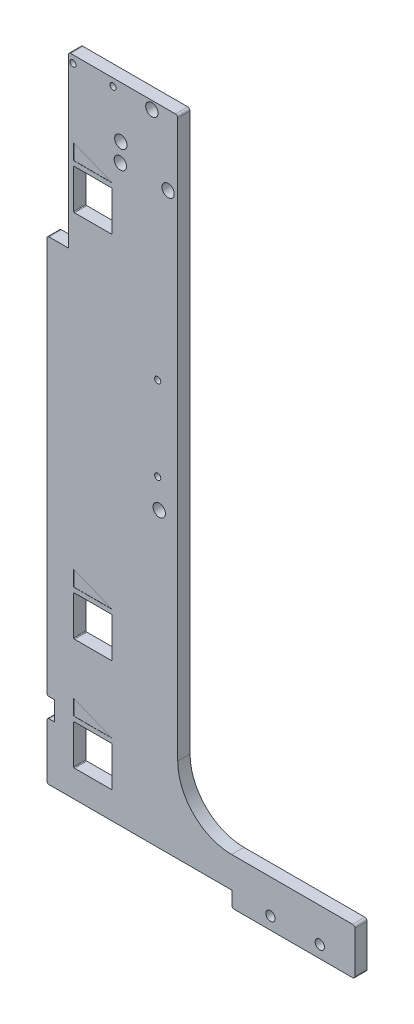
SolidWorks part; units mm, degrees
material "metacrilato"
ref_plane "Alzado" through (0, 0, 0) normal (0, 0, 1) x (1, 0, 0)
ref_plane "Planta" through (0, 0, 0) normal (0, 1, 0) x (1, 0, 0)
ref_plane "Vista lateral" through (0, 0, 0) normal (1, 0, 0) x (0, 0, -1)
sketch "Croquis1" plane through (0, 0, 0) normal (0, 0, 1) x (1, 0, 0)
  line L0 (0, 0) -> (-200, 0)
  line L1 (-200, 0) -> (-200, 428)
  line L2 (-200, 428) -> (-115, 428)
  line L3 (-115, 428) -> (-115, 30)
  line L4 (-115, 30) -> (0, 30)
  line L5 (0, 30) -> (0, 0)
  dimension "D1" = 200
  dimension "D2" = 428
  dimension "D3" = 30
  dimension "D4" = 85
extrude "Base" add sketch "Croquis1" along normal mid plane 8
fillet "Redondeo1" radius 35 1 edges at (-115, 30, 0)
sketch "Croquis2" plane through (0, 0, 4) normal (0, 0, 1) x (1, 0, 0)
  line L0 (-115, 428) -> (-200, 428) construction
  line L1 (-200, 428) -> (-200, 0) construction
  line L3 (0, 0) -> (0, 30) construction
  line L4 (-200, 0) -> (0, 0) construction
  circle A0 centre (-183, 423.2) radius 2
  circle A1 centre (-157, 423.2) radius 2
  circle A2 centre (-128, 272.65) radius 2
  circle A3 centre (-128, 218.35) radius 2
  circle A4 centre (-54.8, 8) radius 3
  circle A5 centre (-22.8, 8) radius 3
  dimension "D1" = 4
  dimension "D2" = 4.8
  dimension "D3" = 17
  dimension "D4" = 26
  dimension "D5" = 54.3
  dimension "D6" = 72
  dimension "D7" = 155.35
  dimension "D9" = 6
  dimension "D10" = 22.8
  dimension "D8" = 32
  dimension "D11" = 8
extrude "Forats guia Left" cut sketch "Croquis2" against normal up to next
sketch "Croquis3" plane through (0, 0, 4) normal (0, 0, 1) x (1, 0, 0)
  circle A0 centre (-127, 176.5) radius 4
  circle A1 centre (-128, 218.35) radius 2 construction
  circle A2 centre (-91.3, 19) radius 4
  circle A3 centre (-127.3, 19) radius 4
  circle A7 centre (-54.8, 8) radius 3 construction
  dimension "D1" = 8
  dimension "D2" = 41.85
  dimension "D3" = 1
  dimension "D4" = 11
  dimension "D5" = 36.5
  dimension "D6" = 36
extrude "Forats Left" [suppressed] cut sketch "Croquis3" against normal through all
sketch "Croquis4" plane through (0, 0, -4) normal (0, 0, -1) x (-1, 0, 0)
  line L0 (115, 65) -> (115, 428) construction
  line L1 (115, 428) -> (200, 428) construction
  circle A0 centre (131.8, 422.75) radius 4
  circle A1 centre (151.95, 394.65) radius 4
  circle A2 centre (152.25, 382.59) radius 4
  circle A3 centre (121.25, 382.59) radius 4
  circle A4 centre (127, 200) radius 4
  point P12 (127, 176.5)
  dimension "D1" = 8
  dimension "D2" = 16.8
  dimension "D3" = 5.25
  dimension "D5" = 33.35
  dimension "D6" = 45.41
  dimension "D8" = 31
  dimension "D10" = 12
  dimension "D9" = 228
  dimension "D4" = 36.95
  dimension "D7" = 6.25
extrude "Forats Right" cut sketch "Croquis4" against normal up to next
sketch "Croquis5" plane through (0, 0, 4) normal (0, 0, 1) x (1, 0, 0)
  line L0 (-200, 428) -> (-200, 0) construction
  line L1 (-182.5, 53.5) -> (-157.5, 53.5)
  line L2 (-182.5, 53.5) -> (-182.5, 27.5)
  line L3 (-182.5, 27.5) -> (-157.5, 27.5)
  line L4 (-157.5, 53.5) -> (-157.5, 27.5)
  line L5 (-182.5, 126) -> (-157.5, 126)
  line L6 (-182.5, 126) -> (-182.5, 100)
  line L7 (-182.5, 100) -> (-157.5, 100)
  line L8 (-157.5, 126) -> (-157.5, 100)
  line L9 (-182.5, 365.7) -> (-157.5, 365.7)
  line L10 (-182.5, 365.7) -> (-182.5, 339.7)
  line L11 (-182.5, 339.7) -> (-157.5, 339.7)
  line L12 (-157.5, 365.7) -> (-157.5, 339.7)
  line L13 (-200, 0) -> (0, 0) construction
  dimension "D1" = 25
  dimension "D2" = 26
  dimension "D3" = 17.5
  dimension "D4" = 27.5
  dimension "D5" = 100
  dimension "D6" = 339.7
extrude "Tatxueles" cut sketch "Croquis5" against normal up to next
fillet "Redondeo3" radius 0.5 12 edges at (-182.5, 53.5, 0) (-157.5, 53.5, 0) (-182.5, 27.5, 0) (-182.5, 126, 0) (-157.5, 126, 0) (-157.5, 100, 0) (-182.5, 100, 0) (-182.5, 365.7, 0) (-157.5, 365.7, 0) (-157.5, 339.7, 0) (-182.5, 339.7, 0) (-157.5, 27.5, 0)
sketch "Croquis7" plane through (0, 0, 4) normal (0, 0, 1) x (1, 0, 0)
  line L0 (-200, 0) -> (0, 0) construction
  line L1 (-79.8, 0) -> (-200, 0)
  line L2 (-79.8, 0) -> (-79.8, 10)
  line L3 (-79.8, 10) -> (-200, 10)
  line L4 (-200, 0) -> (-200, 10)
  line L5 (-200, 428) -> (-200, 0) construction
  line L6 (-115, 428) -> (-200, 428) construction
  line L7 (-200, 336.7) -> (-186, 336.7)
  line L8 (-200, 336.7) -> (-200, 428)
  line L9 (-200, 428) -> (-186, 428)
  line L10 (-186, 336.7) -> (-186, 428)
  line L11 (-182.5, 365.2) -> (-182.5, 340.2) construction
  line L14 (-200, 59.5) -> (-195, 59.5)
  line L15 (-200, 59.5) -> (-200, 47)
  line L16 (-200, 47) -> (-195, 47)
  line L17 (-195, 59.5) -> (-195, 47)
  line L18 (-200, 336.7) -> (-187.5, 336.7)
  line L19 (-200, 336.7) -> (-200, 319.2)
  line L20 (-200, 319.2) -> (-187.5, 319.2)
  line L21 (-187.5, 336.7) -> (-187.5, 319.2)
  line L22 (-115, 428) -> (-200, 428) construction
  circle A0 centre (-54.8, 8) radius 3 construction
  line M43 (-115, 428) -> (-200, 428)
  line M44 (-200, 428) -> (-200, 0)
  dimension "D1" = 10
  dimension "D2" = 25
  dimension "D3" = 3.5
  dimension "D4" = 91.3
  dimension "D5" = 12.5
  dimension "D6" = 17.5
  dimension "D7" = 12.5
  dimension "D8" = 5
  dimension "D9" = 47
extrude "Geometria exterior" cut sketch "Croquis7" against normal up to next contours L17 L14 L16 M44 | L7 L10 M43 M44 | L21 L18 L7 L20 M44 | L3 L4 L1 L2 region at (-193.75, 327.95, 4) region at (-197.5, 53.25, 4) region at (-193, 382.35, 4)
sketch "Croquis8" plane through (0, 0, 4) normal (0, 0, 1) x (1, 0, 0)
  line L0 (-182.5, 66.5) -> (-182.5, 56.5)
  line L1 (-182.5, 56.5) -> (-157.5, 56.5)
  line L2 (-157.5, 56.5) -> (-182.5, 66.5)
  line L3 (-182.5, 129) -> (-182.5, 139)
  line L4 (-182.5, 139) -> (-157.5, 129)
  line L5 (-157.5, 129) -> (-182.5, 129)
  line L6 (-182.5, 368.7) -> (-182.5, 378.7)
  line L7 (-182.5, 378.7) -> (-157.5, 368.7)
  line L8 (-157.5, 368.7) -> (-182.5, 368.7)
  line L9 (-170, 56.5) -> (-170, 53.5) construction
  line L10 (-157.5, 340.2) -> (-157.5, 365.2) construction
  line L11 (-158, 53.5) -> (-182, 53.5) construction
  line L12 (-170, 129) -> (-170, 126) construction
  line L13 (-158, 126) -> (-182, 126) construction
  line L14 (-170, 368.7) -> (-170, 365.7) construction
  line L15 (-158, 365.7) -> (-182, 365.7) construction
  dimension "D1" = 10
  dimension "D2" = 3
extrude "Triangles" cut sketch "Croquis8" against normal blind 0.1
mirror "Simetría1" about plane through (0, 0, 0) normal (0, 0, 1) of "Triangles"
sketch "Croquis9" plane through (0, 0, 4) normal (0, 0, 1) x (1, 0, 0)
  text T0 "<b>L</b>" font "Century Gothic" height in points 200
  text T1 "SigmaX" font "Century Gothic" height in points 28
extrude "L" [suppressed] cut sketch "Croquis9" against normal blind 0.1
sketch "Croquis10" plane through (0, 0, -4) normal (0, 0, -1) x (-1, 0, 0)
  text T0 "<b>R</b>" font "Century Gothic" height in points 200
  text T1 "SigmaX" font "Century Gothic" height in points 28
extrude "R" cut sketch "Croquis10" against normal blind 0.1
fillet "Redondeo7" radius 1.5 10 edges at (-79.8, 0, 0) (0, 0, 0) (0, 30, 0) (-115, 428, 0) (-186, 428, 0) (-187.5, 336.7, 0) (-200, 319.2, 0) (-200, 47, 0) (-200, 10, 0) (-200, 59.5, 0)
sketch "Croquis11" plane through (0, 0, -4) normal (0, 0, -1) x (-1, 0, 0)
  line L0 (186, 336.7) -> (186, 317.8676)
  line L1 (186, 336.7) -> (200.2032, 336.7)
  line L2 (186, 317.8676) -> (200.2032, 317.8676)
  line L3 (200.2032, 336.7) -> (200.2032, 317.8676)
extrude "right cut" cut sketch "Croquis11" against normal up to next
fillet "Redondeo8" radius 1.5 1 edges at (-199.9906, 317.8676, 0)
